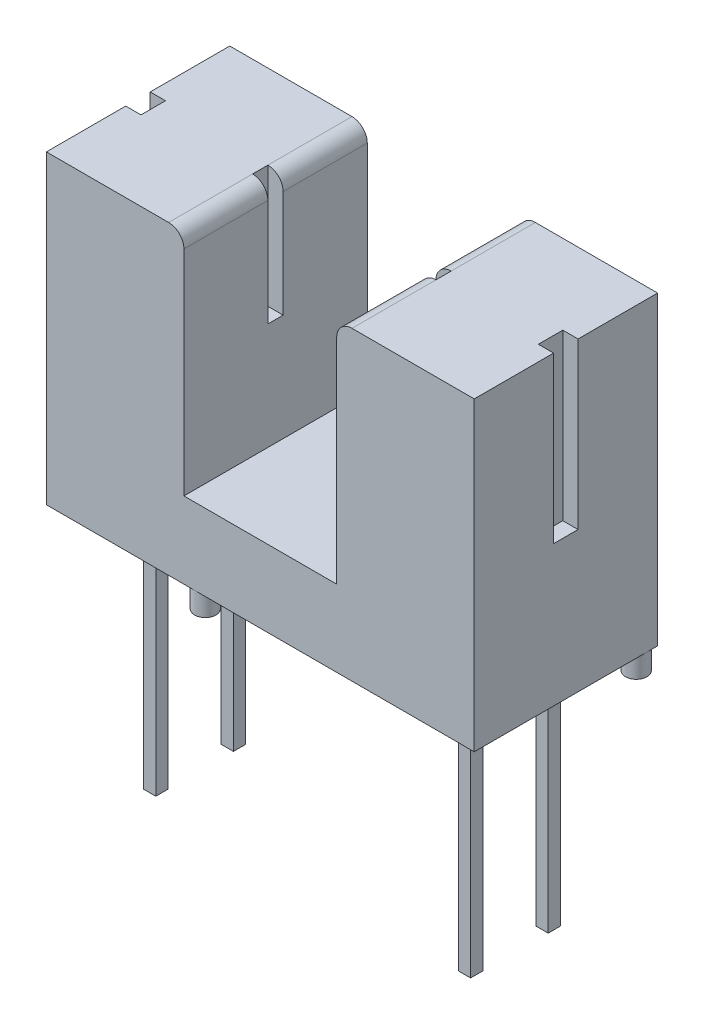
SolidWorks part; units mm, degrees
ref_plane "前视基准面" through (0, 0, 0) normal (0, 0, 1) x (1, 0, 0)
ref_plane "上视基准面" through (0, 0, 0) normal (0, 1, 0) x (1, 0, 0)
ref_plane "右视基准面" through (0, 0, 0) normal (1, 0, 0) x (0, 0, -1)
sketch "草图1" plane through (0, 0, 0) normal (0, 0, 1) x (1, 0, 0)
  line L0 (0, 6.704) -> (0, -11.7189) construction
  line L1 (-7, 5) -> (-2.5, 5)
  line L2 (-7, 5) -> (-7, -5)
  line L3 (-7, -5) -> (7, -5)
  line L4 (7, 5) -> (7, -5)
  line L5 (-7, 5) -> (7, -5) construction
  line L6 (-7, -5) -> (7, 5) construction
  line L7 (2.5, 5) -> (7, 5)
  line L9 (-2.5, 5) -> (-2.5, -2.5)
  line L10 (-2.5, -2.5) -> (2.5, -2.5)
  line L11 (2.5, 5) -> (2.5, -2.5)
  point P0 (0, 0)
  dimension "D1" = 14
  dimension "D2" = 10
  dimension "D3" = 5
  dimension "D4" = 2.5
extrude "凸台-拉伸1" add sketch "草图1" along normal blind 6
fillet "圆角1" radius 0.5 2 edges at (2.5, 5, 3) (-2.5, 5, 3)
sketch "草图2" plane through (0, -5, 0) normal (0, -1, 0) x (1, 0, 0)
  line L0 (-8.0802, 3) -> (8.1696, 3) construction
  line L1 (0, 6.3864) -> (0, -1.1649) construction
  line L3 (-5.15, 4.27) -> (5.15, 4.27) construction
  line L4 (-5.15, 4.27) -> (-5.15, 1.73) construction
  line L5 (-5.15, 1.73) -> (5.15, 1.73) construction
  line L6 (5.15, 4.27) -> (5.15, 1.73) construction
  line L7 (-5.15, 4.27) -> (5.15, 1.73) construction
  line L8 (-5.15, 1.73) -> (5.15, 4.27) construction
  line L9 (-5.35, 4.47) -> (-4.95, 4.47)
  line L10 (-5.35, 4.47) -> (-5.35, 4.07)
  line L11 (-5.35, 4.07) -> (-4.95, 4.07)
  line L12 (-4.95, 4.47) -> (-4.95, 4.07)
  line L13 (-5.35, 4.47) -> (-4.95, 4.07) construction
  line L14 (-5.35, 4.07) -> (-4.95, 4.47) construction
  line L15 (4.95, 4.47) -> (5.35, 4.47)
  line L16 (4.95, 4.47) -> (4.95, 4.07)
  line L17 (4.95, 4.07) -> (5.35, 4.07)
  line L18 (5.35, 4.47) -> (5.35, 4.07)
  line L19 (4.95, 4.47) -> (5.35, 4.07) construction
  line L20 (4.95, 4.07) -> (5.35, 4.47) construction
  line L21 (-5.35, 1.53) -> (-4.95, 1.53)
  line L22 (-5.35, 1.53) -> (-5.35, 1.93)
  line L23 (-5.35, 1.93) -> (-4.95, 1.93)
  line L24 (-4.95, 1.53) -> (-4.95, 1.93)
  line L25 (-5.35, 1.53) -> (-4.95, 1.93) construction
  line L26 (-5.35, 1.93) -> (-4.95, 1.53) construction
  line L27 (4.95, 1.93) -> (5.35, 1.93)
  line L28 (4.95, 1.93) -> (4.95, 1.53)
  line L29 (4.95, 1.53) -> (5.35, 1.53)
  line L30 (5.35, 1.93) -> (5.35, 1.53)
  line L31 (4.95, 1.93) -> (5.35, 1.53) construction
  line L32 (4.95, 1.53) -> (5.35, 1.93) construction
  point P4 (0, 3)
  dimension "D1" = 10.3
  dimension "D2" = 2.54
  dimension "D3" = 0.4
  dimension "D4" = 0.4
  dimension "D5" = 0.4
  dimension "D6" = 0.4
  dimension "D7" = 0.4
  dimension "D8" = 0.4
  dimension "D9" = 0.4
  dimension "D10" = 0.4
extrude "凸台-拉伸2" add sketch "草图2" along normal blind 8
sketch "草图3" plane through (-7, 0, 0) normal (-1, 0, 0) x (0, 0, 1)
  line L0 (3.0034, 5.5455) -> (3.0034, -0.195) construction
  line L1 (6, 5) -> (0, 5) construction
  line L2 (2.6034, 5) -> (3.4034, 5)
  line L3 (2.6034, 5) -> (2.6034, -0.4)
  line L4 (2.6034, -0.4) -> (3.4034, -0.4)
  line L5 (3.4034, 5) -> (3.4034, -0.4)
  dimension "D1" = 0.8
  dimension "D2" = 5.4
extrude "切除-拉伸1" cut sketch "草图3" against normal blind 0.5
sketch "草图4" plane through (7, 0, 0) normal (1, 0, 0) x (0, 0, -1)
  line L1 (-3.4034, 5) -> (-2.6034, 5)
  line L2 (-3.4034, 5) -> (-3.4034, -0.4)
  line L3 (-3.4034, -0.4) -> (-2.6034, -0.4)
  line L4 (-2.6034, 5) -> (-2.6034, -0.4)
extrude "切除-拉伸2" cut sketch "草图4" against normal blind 0.5
sketch "草图5" plane through (-2.5, 0, 0) normal (1, 0, 0) x (0, 0, -1)
  line L0 (-3.0034, 5.9062) -> (-3.0034, -8.6513) construction
  line L1 (-2.6034, 5) -> (-3.4034, 5) construction
  line L2 (-3.2534, 5) -> (-2.7534, 5)
  line L3 (-3.2534, 5) -> (-3.2534, 1)
  line L4 (-3.2534, 1) -> (-2.7534, 1)
  line L5 (-2.7534, 5) -> (-2.7534, 1)
  dimension "D1" = 0.5
  dimension "D2" = 4
extrude "切除-拉伸3" cut sketch "草图5" against normal blind 0.5
sketch "草图6" plane through (2.5, 0, 0) normal (-1, 0, 0) x (0, 0, 1)
  line L0 (3.4034, 5) -> (2.6034, 5) construction
  line L1 (3.2534, 1) -> (2.7534, 1)
  line L2 (3.2534, 1) -> (3.2534, 5)
  line L3 (3.2534, 5) -> (2.7534, 5)
  line L4 (2.7534, 1) -> (2.7534, 5)
extrude "切除-拉伸4" cut sketch "草图6" against normal blind 0.5
sketch "草图7" plane through (0, -5, 0) normal (0, -1, 0) x (1, 0, 0)
  line L0 (-7, 6) -> (7, 6) construction
  line L1 (0, 6.6897) -> (0, -1.6439) construction
  line L2 (7, 6) -> (7, 0) construction
  line L3 (-7, 0) -> (7, 0) construction
  line L4 (-2.5, 6) -> (-2.5, 0) construction
  circle A0 centre (-2.15, 5.65) radius 0.35
  circle A1 centre (6.65, 0.35) radius 0.35
  dimension "D1" = 0.7
  dimension "D2" = 0.7
extrude "凸台-拉伸3" add sketch "草图7" along normal blind 0.7
